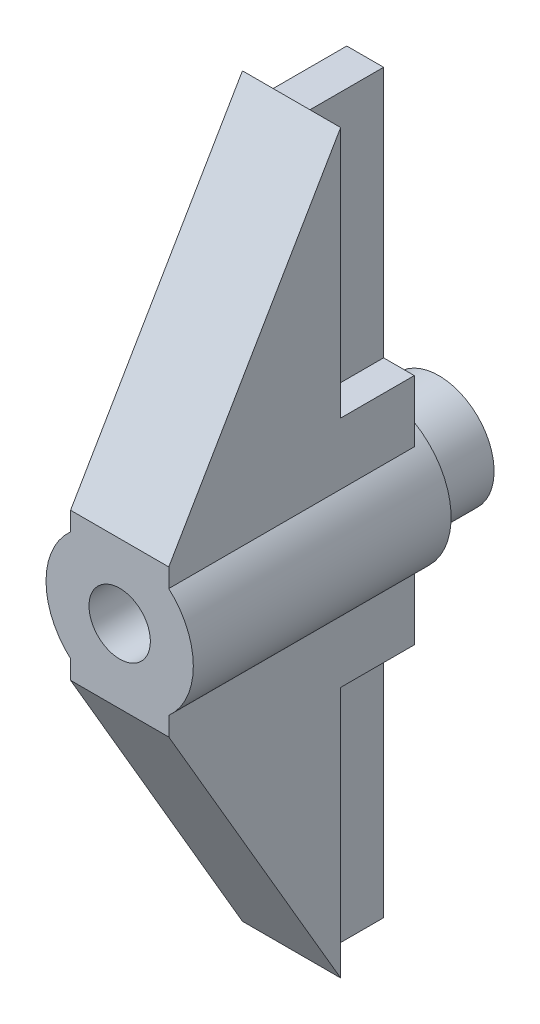
SolidWorks part; units mm, degrees
ref_plane "Front Plane" through (0, 0, 0) normal (0, 0, 1) x (1, 0, 0)
ref_plane "Top Plane" through (0, 0, 0) normal (0, 1, 0) x (1, 0, 0)
ref_plane "Right Plane" through (0, 0, 0) normal (1, 0, 0) x (0, 0, -1)
other "Configuration Table"
sketch "Sketch1" plane through (0, 0, 0) normal (0, 0, 1) x (1, 0, 0)
  circle A0 centre (0, 0) radius 2.5
  circle A1 centre (0, 0) radius 6
  dimension "D1" = 5
  dimension "D2" = 12
extrude "Boss-Extrude1" add sketch "Sketch1" along normal blind 20
sketch "Sketch2" plane through (0, 0, 0) normal (1, 0, 0) x (0, 0, -1)
  line L0 (-20, 6) -> (-20, 3)
  line L2 (-20, 3) -> (0, 3)
  line L3 (-20, 6) -> (-20, -6) construction
  line L5 (0, 3) -> (0, 30)
  line L6 (-20, 6) -> (-6, 30)
  line L7 (-6, 30) -> (0, 30)
  line L8 (0, 6) -> (-20, 6) construction
  point P0 (-20, 6)
  dimension "D1" = 30
  dimension "D2" = 6
  dimension "D3" = 3
extrude "Boss-Extrude2" add sketch "Sketch2" along normal mid plane 8
sketch "Sketch3" plane through (0, 30, 0) normal (0, 1, 0) x (1, 0, 0)
  line L0 (-4, 0) -> (-1.5, 0)
  line L1 (4, 0) -> (-4, 0) construction
  line L2 (-1.5, 0) -> (-1.5, -6)
  line L3 (4, -6) -> (-4, -6) construction
  line L4 (-1.5, -6) -> (-4, -6)
  line L5 (-4, -6) -> (-4, 0)
  line L6 (4, 0) -> (1.5, 0)
  line L7 (1.5, 0) -> (1.5, -6)
  line L8 (1.5, -6) -> (4, -6)
  line L9 (4, -6) -> (4, 0)
  dimension "D1" = 2.5
extrude "Cut-Extrude1" cut sketch "Sketch3" against normal blind 20.5
move or copy body "Body-Move/Copy1" bodies to move or copy 104 copy yes number of copies 1 rotation origin (0, 0, 0) rotation axis (0, 0, 1) rotation angle 180
sketch "Sketch4" plane through (0, 0, 0) normal (0, 0, -1) x (-1, 0, 0)
  circle A0 centre (0, 0) radius 6
extrude "Boss-Extrude3" add sketch "Sketch4" along normal blind 1
sketch "Sketch5" plane through (0, 0, -1) normal (0, 0, -1) x (-1, 0, 0)
  circle A0 centre (0, 0) radius 4.5
extrude "Boss-Extrude4" add sketch "Sketch5" along normal blind 5
sketch "Sketch6" plane through (0, 0, -6) normal (0, 0, -1) x (-1, 0, 0)
  circle A0 centre (0, 0) radius 3.5
extrude "Cut-Extrude2" cut sketch "Sketch6" against normal blind 5
